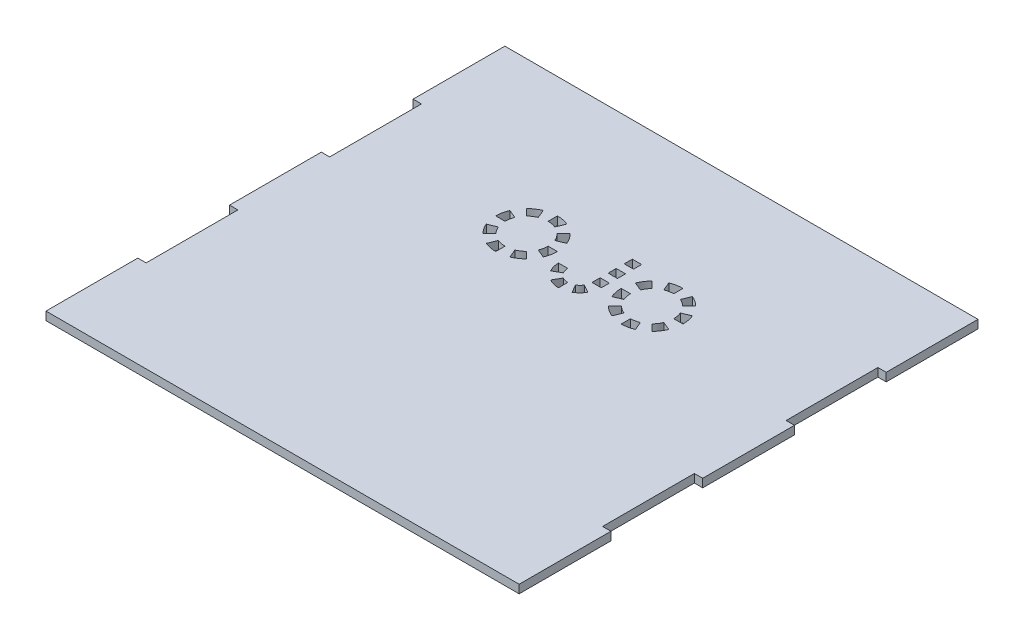
SolidWorks part; units mm, degrees
ref_plane "Ön Düzlem" through (0, 0, 0) normal (0, 0, 1) x (1, 0, 0)
ref_plane "Üst Düzlem" through (0, 0, 0) normal (0, 1, 0) x (1, 0, 0)
ref_plane "Sağ Düzlem" through (0, 0, 0) normal (1, 0, 0) x (0, 0, -1)
sketch "Sketch1" plane through (0, 0, 0) normal (0, 1, 0) x (1, 0, 0)
  line L1 (76.7, -74.385) -> (-76.7, -74.385)
  line L2 (76.7, -74.385) -> (76.7, -44.631)
  line L3 (76.7, 74.385) -> (-76.7, 74.385)
  line L4 (-76.7, -74.385) -> (-76.7, -44.631)
  line L5 (74, -14.877) -> (74, -44.631)
  line L6 (-74, 44.631) -> (-74, 14.877)
  line L7 (-76.7, -14.877) -> (-76.7, 14.877)
  line L9 (-76.7, 44.631) -> (-76.7, 74.385)
  line L11 (-74, -14.877) -> (-74, -44.631)
  line L12 (-76.7, -44.631) -> (-74, -44.631)
  line L13 (-76.7, -14.877) -> (-74, -14.877)
  line L14 (-76.7, 14.877) -> (-74, 14.877)
  line L15 (-76.7, 44.631) -> (-74, 44.631)
  line L17 (76.7, -44.631) -> (74, -44.631)
  line L18 (76.7, -14.877) -> (74, -14.877)
  line L19 (76.7, 14.877) -> (74, 14.877)
  line L20 (76.7, 44.631) -> (74, 44.631)
  line L22 (76.7, 44.631) -> (76.7, 74.385)
  line L23 (76.7, -14.877) -> (76.7, 14.877)
  line L26 (74, 44.631) -> (74, 14.877)
  line L73 (-13.442, 18.1649) -> (-15.5633, 20.2862)
  line L74 (-11.2743, 21.4091) -> (-14.0459, 22.5572)
  line L75 (-10.5131, 25.2359) -> (-13.5131, 25.2359)
  line L76 (-11.2743, 29.0628) -> (-14.0459, 27.9147)
  line L77 (-13.442, 32.307) -> (-15.5633, 30.1857)
  line L78 (-16.6862, 34.4747) -> (-17.8343, 31.7031)
  line L79 (-20.5131, 35.2359) -> (-20.5131, 32.2359)
  line L80 (-23.1918, 31.7031) -> (-24.3399, 34.4747)
  line L81 (-25.4628, 30.1857) -> (-27.5841, 32.307)
  line L82 (-26.9802, 27.9147) -> (-29.7519, 29.0628)
  line L83 (-27.5131, 25.2359) -> (-30.5131, 25.2359)
  line L84 (-26.9802, 22.5572) -> (-29.7519, 21.4091)
  line L85 (-25.4628, 20.2862) -> (-27.5841, 18.1649)
  line L86 (-23.1918, 18.7688) -> (-24.3399, 15.9971)
  line L87 (-20.5131, 18.2359) -> (-20.5131, 15.2359)
  line L88 (-16.6862, 15.9971) -> (-17.8343, 18.7688)
  line L89 (22.8694, 18.7688) -> (24.0174, 15.9971)
  line L90 (20.1906, 18.2359) -> (20.1906, 15.2359)
  line L91 (26.6578, 22.5572) -> (29.4294, 21.4091)
  line L92 (25.1403, 20.2862) -> (27.2617, 18.1649)
  line L93 (26.6578, 27.9147) -> (29.4294, 29.0628)
  line L94 (27.1906, 25.2359) -> (30.1906, 25.2359)
  line L95 (22.8694, 31.7031) -> (24.0174, 34.4747)
  line L96 (25.1403, 30.1857) -> (27.2617, 32.307)
  line L97 (16.3638, 34.4747) -> (17.5118, 31.7031)
  line L98 (20.1906, 35.2359) -> (20.1906, 32.2359)
  line L99 (10.9518, 29.0628) -> (13.7234, 27.9147)
  line L100 (13.1195, 32.307) -> (15.2409, 30.1857)
  line L101 (10.9518, 21.4091) -> (13.7234, 22.5572)
  line L102 (10.1906, 25.2359) -> (13.1906, 25.2359)
  line L103 (13.1195, 18.1649) -> (15.2409, 20.2862)
  line L104 (16.3638, 15.9971) -> (17.5118, 18.7688)
  line L105 (-7.1033, 22.179) -> (-4.1003, 22.179)
  line L106 (6.7828, 35.2359) -> (3.7692, 35.2359)
  line L107 (3.7797, 22.179) -> (3.7776, 24.7904)
  line L108 (6.7828, 22.179) -> (6.7828, 24.7904)
  line L109 (3.7755, 27.4018) -> (3.7734, 30.0132)
  line L110 (3.7713, 32.6246) -> (3.7692, 35.2359)
  line L111 (3.7713, 32.6246) -> (6.7828, 32.6246)
  line L112 (3.7734, 30.0132) -> (6.7828, 30.0132)
  line L113 (3.7755, 27.4018) -> (6.7828, 27.4018)
  line L114 (3.7776, 24.7904) -> (6.7828, 24.7904)
  line L115 (3.7797, 22.179) -> (6.7828, 22.179)
  line L116 (-3.5724, 20.209) -> (-6.1731, 18.7075)
  line L117 (-3.6318, 16.1661) -> (-2.1303, 18.7669)
  line L118 (-0.1603, 18.239) -> (-0.1603, 15.2359)
  line L119 (3.3113, 16.1661) -> (1.8097, 18.7669)
  line L120 (5.8526, 18.7075) -> (3.2519, 20.209)
  line L121 (6.7828, 32.6246) -> (6.7828, 35.2359)
  line L122 (6.7828, 27.4018) -> (6.7828, 30.0132)
  arc A38 (-11.2743, 29.0628) -> (-13.442, 32.307) centre (-20.5131, 25.2359) ccw
  arc A39 (-23.1918, 31.7031) -> (-25.4628, 30.1857) centre (-20.5131, 25.2359) ccw
  arc A40 (-16.6862, 34.4747) -> (-20.5131, 35.2359) centre (-20.5131, 25.2359) ccw
  arc A41 (-24.3399, 34.4747) -> (-27.5841, 32.307) centre (-20.5131, 25.2359) ccw
  arc A42 (-29.7519, 29.0628) -> (-30.5131, 25.2359) centre (-20.5131, 25.2359) ccw
  arc A43 (-29.7519, 21.4091) -> (-27.5841, 18.1649) centre (-20.5131, 25.2359) ccw
  arc A44 (-24.3399, 15.9971) -> (-20.5131, 15.2359) centre (-20.5131, 25.2359) ccw
  arc A45 (-16.6862, 15.9971) -> (-13.442, 18.1649) centre (-20.5131, 25.2359) ccw
  arc A46 (-11.2743, 21.4091) -> (-10.5131, 25.2359) centre (-20.5131, 25.2359) ccw
  arc A47 (-17.8343, 31.7031) -> (-20.5131, 32.2359) centre (-20.5131, 25.2359) ccw
  arc A48 (-14.0459, 27.9147) -> (-15.5633, 30.1857) centre (-20.5131, 25.2359) ccw
  arc A49 (-14.0459, 22.5572) -> (-13.5131, 25.2359) centre (-20.5131, 25.2359) ccw
  arc A50 (-17.8343, 18.7688) -> (-15.5633, 20.2862) centre (-20.5131, 25.2359) ccw
  arc A51 (-23.1918, 18.7688) -> (-20.5131, 18.2359) centre (-20.5131, 25.2359) ccw
  arc A52 (-26.9802, 22.5572) -> (-25.4628, 20.2862) centre (-20.5131, 25.2359) ccw
  arc A53 (-26.9802, 27.9147) -> (-27.5131, 25.2359) centre (-20.5131, 25.2359) ccw
  arc A54 (22.8694, 18.7688) -> (20.1906, 18.2359) centre (20.1906, 25.2359) cw
  arc A55 (24.0174, 15.9971) -> (20.1906, 15.2359) centre (20.1906, 25.2359) cw
  arc A56 (26.6578, 22.5572) -> (25.1403, 20.2862) centre (20.1906, 25.2359) cw
  arc A57 (29.4294, 21.4091) -> (27.2617, 18.1649) centre (20.1906, 25.2359) cw
  arc A58 (26.6578, 27.9147) -> (27.1906, 25.2359) centre (20.1906, 25.2359) cw
  arc A59 (29.4294, 29.0628) -> (30.1906, 25.2359) centre (20.1906, 25.2359) cw
  arc A60 (22.8694, 31.7031) -> (25.1403, 30.1857) centre (20.1906, 25.2359) cw
  arc A61 (24.0174, 34.4747) -> (27.2617, 32.307) centre (20.1906, 25.2359) cw
  arc A62 (16.3638, 34.4747) -> (20.1906, 35.2359) centre (20.1906, 25.2359) cw
  arc A63 (17.5118, 31.7031) -> (20.1906, 32.2359) centre (20.1906, 25.2359) cw
  arc A64 (10.9518, 29.0628) -> (13.1195, 32.307) centre (20.1906, 25.2359) cw
  arc A65 (13.7234, 27.9147) -> (15.2409, 30.1857) centre (20.1906, 25.2359) cw
  arc A66 (10.9518, 21.4091) -> (10.1906, 25.2359) centre (20.1906, 25.2359) cw
  arc A67 (13.7234, 22.5572) -> (13.1906, 25.2359) centre (20.1906, 25.2359) cw
  arc A68 (16.3638, 15.9971) -> (13.1195, 18.1649) centre (20.1906, 25.2359) cw
  arc A69 (17.5118, 18.7688) -> (15.2409, 20.2862) centre (20.1906, 25.2359) cw
  arc A70 (-7.1033, 22.179) -> (-6.1731, 18.7075) centre (-0.1603, 22.179) ccw
  arc A71 (-4.1003, 22.179) -> (-3.5724, 20.209) centre (-0.1603, 22.179) ccw
  arc A72 (-3.6318, 16.1661) -> (-0.1603, 15.2359) centre (-0.1603, 22.179) ccw
  arc A73 (3.3113, 16.1661) -> (5.8526, 18.7075) centre (-0.1603, 22.179) ccw
  arc A74 (1.8097, 18.7669) -> (3.2519, 20.209) centre (-0.1603, 22.179) ccw
  arc A75 (-2.1303, 18.7669) -> (-0.1603, 18.239) centre (-0.1603, 22.179) ccw
  point P0 (0, 0)
  point P15 (0, 0)
  dimension "D1" = 148.77
  dimension "D2" = 153.4
extrude "Boss-Extrude1" add sketch "Sketch1" along normal blind 2.7
